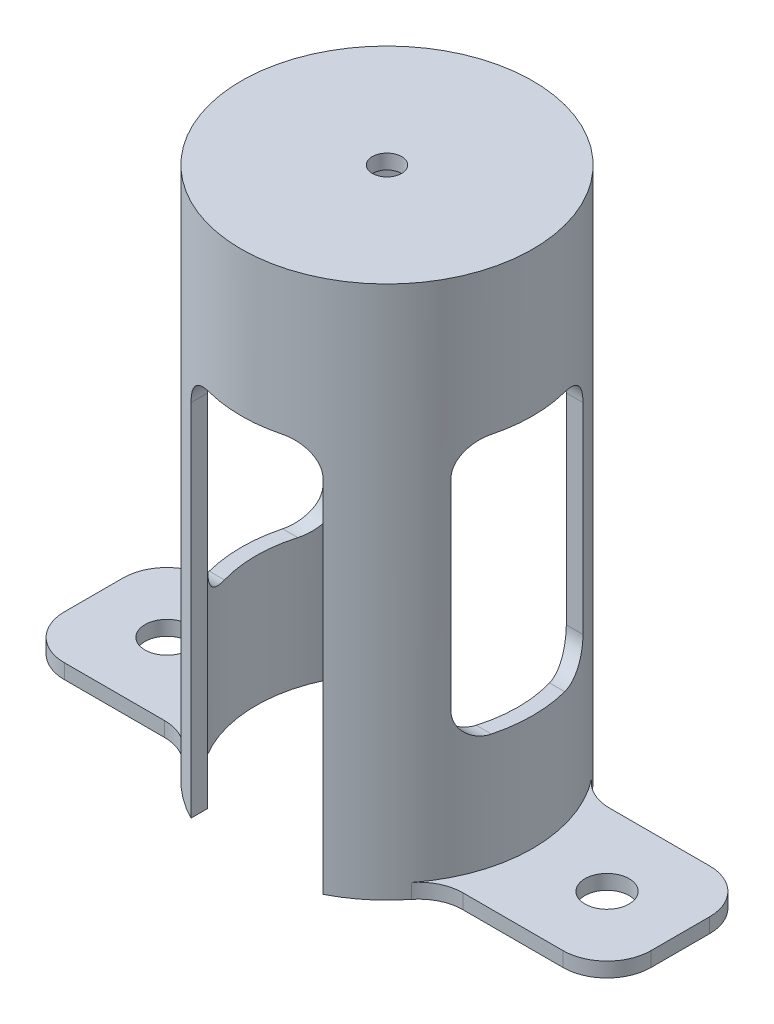
SolidWorks part; units mm, degrees
material "6061-T6 (SS)"
ref_plane "Front Plane" through (0, 0, 0) normal (0, 0, 1) x (1, 0, 0)
ref_plane "Top Plane" through (0, 0, 0) normal (0, 1, 0) x (1, 0, 0)
ref_plane "Right Plane" through (0, 0, 0) normal (1, 0, 0) x (0, 0, -1)
sketch "Sketch2" plane through (0, 0, 0) normal (0, 1, 0) x (1, 0, 0)
  circle A1 centre (0, 0) radius 9.9375
  dimension "D2" = 19.875
extrude "Boss-Extrude1" add sketch "Sketch2" along normal blind 35.384
sketch "Sketch4" plane through (0, 35.384, 0) normal (0, 1, 0) x (1, 0, 0)
  circle A0 centre (0, 0) radius 1
  dimension "D1" = 2
extrude "Cut-Extrude2" cut sketch "Sketch4" against normal through all
sketch "Sketch11" plane through (0, 0, 0) normal (0, -1, 0) x (1, 0, 0)
  line L0 (8.588, 5) -> (20, 5)
  line L1 (-20, 5) -> (-8.588, 5)
  line L2 (-20, 5) -> (-20, -5)
  line L3 (-20, -5) -> (-8.588, -5)
  line L4 (20, 5) -> (20, -5)
  line L5 (-20, 5) -> (20, -5) construction
  line L6 (-20, -5) -> (20, 5) construction
  line L7 (8.588, -5) -> (20, -5)
  arc A0 (8.588, 5) -> (-8.588, 5) centre (0, 0) ccw
  circle A1 centre (0, 0) radius 8.9375
  arc A2 (-8.588, -5) -> (8.588, -5) centre (0, 0) ccw
  point P0 (0, 0)
  dimension "D3" = 19.875
  dimension "D4" = 17.875
  dimension "D1" = 10
  dimension "D2" = 40
extrude "Boss-Extrude2" add sketch "Sketch11" along normal blind 1
sketch "Sketch12" plane through (0, 0, 0) normal (0, -1, 0) x (1, 0, 0)
  circle A0 centre (0, 0) radius 8.9375
  dimension "D1" = 17.875
extrude "Cut-Extrude7" cut sketch "Sketch12" against normal blind 34.384
ref_plane "Plane4" through (0, 0, 30) normal (0, 0, 1) x (1, 0, 0)
sketch "Sketch13" plane through (0, 0, 30) normal (0, 0, 1) x (1, 0, 0)
  line L0 (0, -10.9313) -> (0, 10.9313) construction
  line L1 (-4.5, 25.538) -> (4.5, 25.538)
  line L2 (-4.5, 25.538) -> (-4.5, -1)
  line L3 (-4.5, -1) -> (4.5, -1)
  line L4 (4.5, 25.538) -> (4.5, -1)
  line L5 (-4.5, 25.538) -> (4.5, -1) construction
  line L6 (-4.5, -1) -> (4.5, 25.538) construction
  line L7 (-8.588, -1) -> (8.588, -1) construction
  point P0 (0, 12.269)
  dimension "D1" = 26.538
  dimension "D2" = 9
extrude "Cut-Extrude8" cut sketch "Sketch13" against normal through all
ref_plane "Plane5" through (30, 0, 0) normal (1, 0, 0) x (0, 0, -1)
sketch "Sketch14" plane through (30, 0, 0) normal (1, 0, 0) x (0, 0, -1)
  line L0 (0, 20.0112) -> (0, -20.0112) construction
  line L1 (-4.5, 25.538) -> (4.5, 25.538)
  line L2 (-4.5, 25.538) -> (-4.5, 7.846)
  line L3 (-4.5, 7.846) -> (4.5, 7.846)
  line L4 (4.5, 25.538) -> (4.5, 7.846)
  line L5 (-4.5, 25.538) -> (4.5, 7.846) construction
  line L6 (-4.5, 7.846) -> (4.5, 25.538) construction
  line L7 (5, -1) -> (-5, -1) construction
  point P0 (0, 16.692)
  dimension "D2" = 9
  dimension "D1" = 17.692
  dimension "D3" = 17.692
extrude "Cut-Extrude9" cut sketch "Sketch14" against normal through all
fillet "Fillet3" radius 2 12 edges at (4.5, 25.538, -8.2911) (-4.5, 25.538, -8.2911) (-4.5, 25.538, 8.2911) (4.5, 25.538, 8.2911) (-8.2911, 25.538, 4.5) (-8.2911, 25.538, -4.5) (-8.2911, 7.846, -4.5) (-8.2911, 7.846, 4.5) (8.2911, 7.846, 4.5) (8.2911, 25.538, 4.5) (8.2911, 25.538, -4.5) (8.2911, 7.846, -4.5)
fillet "Fillet4" radius 3 8 edges at (8.588, -0.5, -5) (20, -0.5, -5) (8.588, -0.5, 5) (20, -0.5, 5) (-8.588, -0.5, 5) (-20, -0.5, -5) (-8.588, -0.5, -5) (-20, -0.5, 5)
sketch "Sketch15" plane through (0, 0, 0) normal (0, 1, 0) x (1, 0, 0)
  line L0 (-20.0112, 0) -> (20.0112, 0) construction
  line L1 (20, 2) -> (20, -2) construction
  line L2 (-20, -2) -> (-20, 2) construction
  circle A0 centre (-15, 0) radius 1.5
  circle A1 centre (15, 0) radius 1.5
  dimension "D3" = 3
  dimension "D4" = 3
  dimension "D1" = 5
  dimension "D2" = 5
extrude "Cut-Extrude10" cut sketch "Sketch15" against normal up to next
equation "\"FrangiboltTotalDiameter\"= 0.625in"
equation "\"FrangiboltTotalLength\"= 0.960in"
equation "\"FrangiboltThruHoleDiameter\"= 0.169in"
equation "\"EnclosureWallThickness\"= 1mm"
equation "\"EnclosureWallSpacing\"= 1mm"
equation "\"EnclosureInnerDiameter\"= \"FrangiboltTotalDiameter\" + 2 * \"EnclosureWallSpacing\""
equation "\"EnclosureOuterDiameter\"= \"FrangiboltTotalDiameter\" + 2 * \"EnclosureWallSpacing\" + 2 * \"EnclosureWallThickness\""
equation "\"EnclosureTotalLength\"= \"FrangiboltTotalLength\" + \"DamperLength\" + \"EnclosureWallThickness\""
equation "\"D2@Sketch2\"=\"EnclosureOuterDiameter\""
equation "\"D1@Boss-Extrude1\"=\"EnclosureTotalLength\""
equation "\"DamperLength\"= 10mm"
equation "\"EnclosureLip\"= 5mm"
equation "\"FrangiboltBoxWidth\"= 7mm"
equation "\"EnclosureMountingStandoff\"= 40"
equation "\"D2@Sketch11\"=\"EnclosureMountingStandoff\""
equation "\"D3@Sketch11\"=\"EnclosureOuterDiameter\""
equation "\"D4@Sketch11\"=\"EnclosureInnerDiameter\""
equation "\"D1@Boss-Extrude2\"=\"EnclosureWallThickness\""
equation "\"D1@Sketch12\"=\"EnclosureInnerDiameter\""
equation "\"D1@Cut-Extrude7\"=\"EnclosureTotalLength\"-\"EnclosureWallThickness\""
equation "\"D1@Sketch13\"=\"EnclosureTotalLength\"*0.75"
equation "\"D2@Sketch13\"=\"FrangiboltBoxWidth\"+2mm"
equation "\"D1@Sketch14\"=\"EnclosureTotalLength\"*0.5"
equation "\"D2@Sketch14\"=\"FrangiboltBoxWidth\"+2mm"
equation "\"D3@Sketch14\"=\"EnclosureTotalLength\"*0.5"
equation "\"EnclosureMountingHole\"= 3"
equation "\"D3@Sketch15\"=\"EnclosureMountingHole\""
equation "\"D4@Sketch15\"=\"EnclosureMountingHole\""
